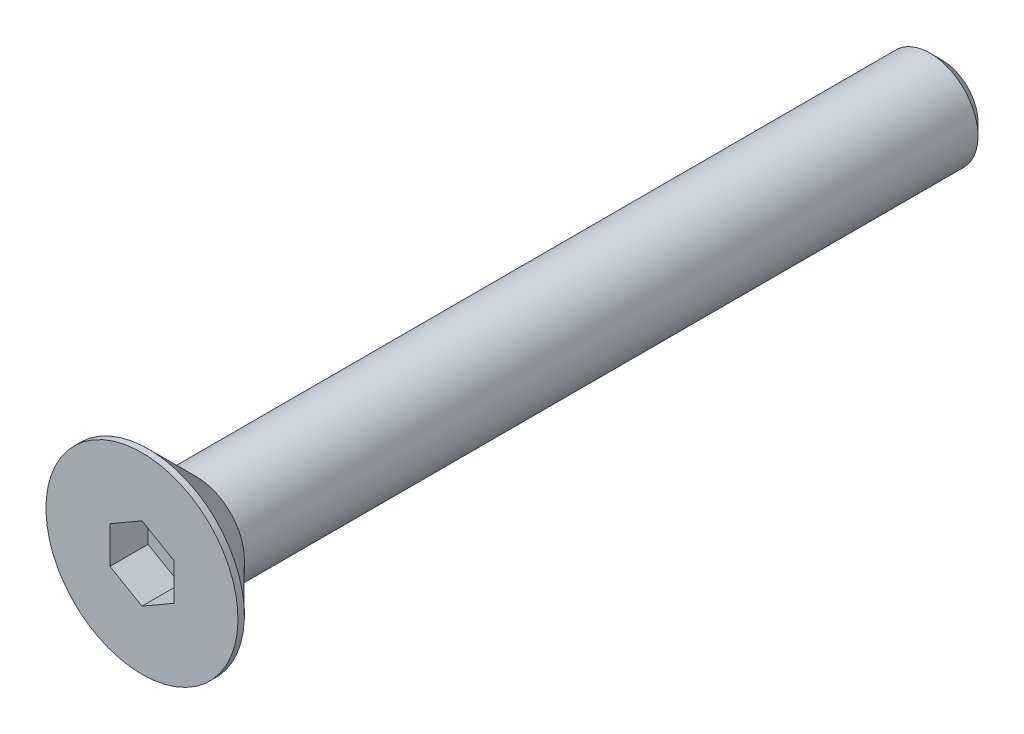
SolidWorks part; units mm, degrees
ref_plane "Front" through (0, 0, 0) normal (0, 0, 1) x (1, 0, 0)
ref_plane "Top" through (0, 0, 0) normal (0, 1, 0) x (1, 0, 0)
ref_plane "Right" through (0, 0, 0) normal (1, 0, 0) x (0, 0, -1)
sketch "Sketch1" plane through (0, 0, 0) normal (1, 0, 0) x (0, 0, -1)
  line L0 (0, 3) -> (0.2, 3) construction
  line L1 (0.2, 3) -> (1.7, 1.5) construction
  line L2 (0, 1.5) -> (25, 1.5)
  line L3 (25, 1.5) -> (25, 0)
  line L4 (25, 0) -> (0, 0)
  line L5 (0, 0) -> (0, 3) construction
  line L6 (0, 3) -> (0, -3) construction
  line L7 (25, 1.5) -> (25, -1.5) construction
  line L8 (0, -3) -> (0.2, -3) construction
  line L9 (0.2, -3) -> (1.7, -1.5) construction
  line L11 (0, 1.5) -> (0, 0)
  line L12 (1.7, 1.5) -> (1.7, 0) construction
revolve "Revolve1" add sketch "Sketch1" angle 360 mid plane about L4
sketch "Sketch3" plane through (0, 0, -25) normal (0, 0, -1) x (-1, 0, 0)
  circle A0 centre (0, 0) radius 1.5
curve "Helix/Spiral1" [suppressed] pitch 0.5 height 25 turns 50
sketch "Sketch2" plane through (0, 0, 0) normal (1, 0, 0) x (0, 0, -1)
  line L0 (25, 1.5) -> (25.4375, 1.5)
  line L1 (25.4375, 1.5) -> (25.25, 1.1752)
  line L2 (25.25, 1.1752) -> (25.1875, 1.1752)
  line L3 (25.1875, 1.1752) -> (25, 1.5)
  line L4 (25.0938, 1.3376) -> (25.3438, 1.3376) construction
  dimension "D1" = 60
  dimension "D2" = 0.0625
  dimension "D3" = 0.25
chamfer "Chamfer1" distance 0.375 angle 45 1 edges at (0, 1.5, -25)
sweep "Cut-Sweep1" [suppressed] cut profiles "Sketch2" path "Helix/Spiral1"
sketch "Sketch7" plane through (0, 0, 0) normal (1, 0, 0) x (0, 0, -1)
  line L0 (0, 3) -> (0.2, 3) construction
  line L1 (0.2, 3) -> (1.7, 1.5) construction
  line L2 (0, 3) -> (0.2, 3)
  line L3 (0.2, 3) -> (1.7, 1.5)
  line L4 (1.7, 1.5) -> (1.7, 0) construction
  line L5 (1.7, 1.5) -> (1.7, 0)
  line L7 (0, 0) -> (0, 3) construction
  line L8 (0, 0) -> (0, 3)
  line L9 (0, 0) -> (1.7, 0)
  line L10 (3.3, 0) -> (-3.3, 0) construction
revolve "Revolve2" add sketch "Sketch7" angle 360 mid plane about L9
ref_plane "Plane1" through (0, 0, -1.7) normal (0, 0, 1) x (1, 0, 0)
sketch "Sketch8" plane through (0, 0, -1.7) normal (0, 0, 1) x (1, 0, 0)
  circle A0 centre (0, 0) radius 1.5
extrude "Boss-Extrude1" add sketch "Sketch8" against normal through all draft 45
sketch "Sketch5" plane through (0, 0, 0) normal (0, 0, 1) x (1, 0, 0)
  line L1 (1, -0.5774) -> (1, 0.5774)
  line L2 (1, 0.5774) -> (0, 1.1547)
  line L3 (0, 1.1547) -> (-1, 0.5774)
  line L4 (-1, 0.5774) -> (-1, -0.5774)
  line L5 (-1, -0.5774) -> (0, -1.1547)
  line L6 (0, -1.1547) -> (1, -0.5774)
  circle A0 centre (0, 0) radius 1 construction
  dimension "Hex" = 2
extrude "Cut-Extrude2" cut sketch "Sketch5" against normal blind 1.19
sketch "Sketch6" plane through (0, 0, 0) normal (0, 0, 1) x (1, 0, 0)
  circle A0 centre (0, 0) radius 1.1547
extrude "Cut-Extrude3" [suppressed] cut sketch "Sketch6" against normal blind 1.19 draft 45
sketch "Sketch9" [suppressed] plane through (0, 0, -5.5) normal (0, 0, 1) x (1, 0, 0)
  circle A1 centre (0, 0) radius 5
  circle A2 centre (0, 0) radius 5
  point P0 (0, 5)
  dimension "D1" = 0
extrude "Boss-Extrude2" [suppressed] add sketch "Sketch9" against normal offset from surface (18.5 mm away) 26 up to face at (0, 1.125, -25)
fillet "Fillet1" [suppressed] radius 0.3
sketch "Sketch10" plane through (0, 0, 0) normal (1, 0, 0) x (0, 0, -1)
  line L0 (25, 1.5) -> (25, -1.5) construction
  point P0 (24.25, -1.5)
  dimension "D1" = 0.75
equation "\"D3@Helix/Spiral1\" = \"Lg@Sketch1\""
equation "\"D2@Sketch2\" = \"D4@Helix/Spiral1\" * .125"
equation "\"D3@Sketch2\" = \"D4@Helix/Spiral1\" * .5"
equation "\"D1@Chamfer1\" = \"D4@Helix/Spiral1\" * .75"
equation "\"D1@Cut-Extrude2\" = \"Head Ht@Sketch1\" * .7"
equation "\"D1@Sketch10\" = \"D4@Helix/Spiral1\" * 1.5"
equation "\"D1@Cut-Extrude3\" = \"D1@Cut-Extrude2\""
equation "\"D1@Fillet1\" = \"Dia@Sketch1\" * .1"
